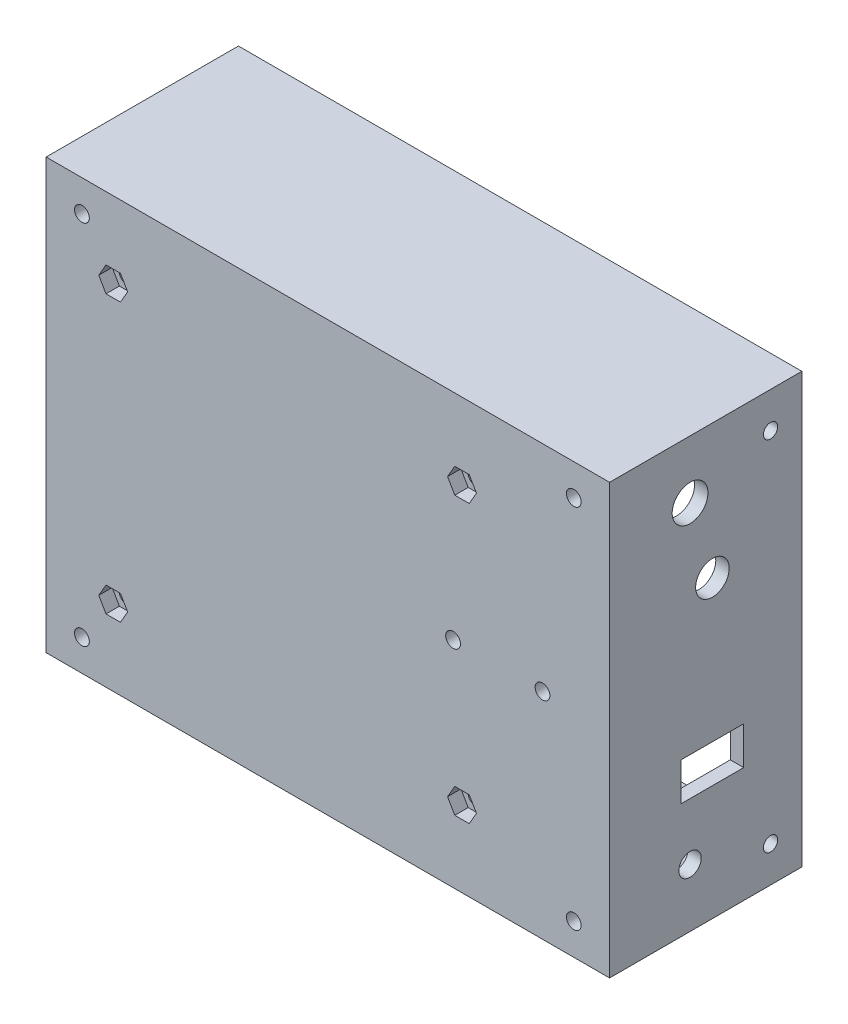
SolidWorks part; units mm, degrees
ref_plane "Front Plane" through (0, 0, 0) normal (0, 0, 1) x (1, 0, 0)
ref_plane "Top Plane" through (0, 0, 0) normal (0, 1, 0) x (1, 0, 0)
ref_plane "Right Plane" through (0, 0, 0) normal (1, 0, 0) x (0, 0, -1)
sketch "Sketch1" plane through (0, 0, 0) normal (0, 0, 1) x (1, 0, 0)
  line L1 (-60, -45) -> (60, -45)
  line L2 (-60, -45) -> (-60, 45)
  line L3 (-60, 45) -> (60, 45)
  line L4 (60, -45) -> (60, 45)
  line L5 (-60, -45) -> (60, 45) construction
  line L6 (-60, 45) -> (60, -45) construction
  line L7 (-48, -31) -> (30, -31)
  line L8 (-48, -31) -> (-48, 31)
  line L9 (-48, 31) -> (30, 31)
  line L10 (30, -31) -> (30, 31)
  line L11 (-48, -31) -> (30, 31) construction
  line L12 (-48, 31) -> (30, -31) construction
  circle A0 centre (-48, 31) radius 1.65
  circle A1 centre (30, 31) radius 1.65
  circle A2 centre (30, -31) radius 1.65
  circle A3 centre (-48, -31) radius 1.65
  circle A4 centre (-55, 41) radius 1.65
  circle A5 centre (55, 41) radius 1.65
  circle A6 centre (55, -41) radius 1.65
  circle A7 centre (-55, -41) radius 1.65
  point P0 (0, 0)
  point P6 (-9, 0)
  dimension "D7" = 3.3
  dimension "D8" = 4
  dimension "D9" = 5
  dimension "D10" = 5
  dimension "D11" = 4
  dimension "D12" = 3.3
  dimension "D13" = 5
  dimension "D14" = 4
  dimension "D15" = 4
  dimension "D16" = 5
  dimension "D1" = 90
  dimension "D2" = 120
  dimension "D3" = 62
  dimension "D4" = 78
  dimension "D5" = 14
  dimension "D6" = 30
extrude "Boss-Extrude2" add sketch "Sketch1" along normal blind 4 contours L1 L4 L3 L2 A3 L8 A0 L9 A1 L10 A2 L7 | A3 L7 A2 L10 A1 L9 A0 L8 region at (-58.5, 0, 0) region at (-9, 0, 0)
sketch "Sketch2" plane through (0, 0, 4) normal (0, 0, 1) x (1, 0, 0)
  line L1 (60, -45) -> (-60, -45)
  line L2 (60, -45) -> (60, 45)
  line L3 (60, 45) -> (-60, 45)
  line L4 (-60, -45) -> (-60, 45)
  line L5 (60, -45) -> (-60, 45) construction
  line L6 (60, 45) -> (-60, -45) construction
  line L7 (63, -48) -> (-63, -48)
  line L8 (63, -48) -> (63, 48)
  line L9 (63, 48) -> (-63, 48)
  line L10 (-63, -48) -> (-63, 48)
  line L11 (63, -48) -> (-63, 48) construction
  line L12 (63, 48) -> (-63, -48) construction
  point P0 (0, 0)
  point P7 (0, 0)
  dimension "D1" = 3
  dimension "D2" = 3
extrude "Boss-Extrude3" add sketch "Sketch2" against normal blind 43
sketch "Sketch3" plane through (-63, 0, 0) normal (-1, 0, 0) x (0, 0, 1)
  line L0 (-39, 48) -> (-39, -48) construction
  line L1 (-39, 48) -> (4, 48) construction
  line L2 (-39, -48) -> (4, -48) construction
  circle A0 centre (-32, -40) radius 1.6
  circle A1 centre (-32, 40) radius 1.6
  dimension "D1" = 3.2
  dimension "D2" = 7
  dimension "D3" = 8
  dimension "D4" = 8
  dimension "D5" = 7
  dimension "D6" = 3.2
extrude "Cut-Extrude1" cut sketch "Sketch3" against normal up to surface (126 mm away) up to face at (63, 0, -17.5)
sketch "Sketch4" plane through (63, 0, 0) normal (1, 0, 0) x (0, 0, -1)
  line L0 (39, -48) -> (39, 48) construction
  line L6 (39, 48) -> (-4, 48) construction
  line L9 (12, -22.25) -> (26, -22.25)
  line L10 (12, -22.25) -> (12, -13.75)
  line L11 (12, -13.75) -> (26, -13.75)
  line L12 (26, -22.25) -> (26, -13.75)
  line L13 (12, -22.25) -> (26, -13.75) construction
  line L14 (12, -13.75) -> (26, -22.25) construction
  line L19 (39, -48) -> (-4, -48) construction
  circle A1 centre (19, 18) radius 3.75
  point P0 (21, 0)
  point P8 (19, -18)
  dimension "D4" = 7.5
  dimension "D5" = 8.5
  dimension "D6" = 20
  dimension "D7" = 14
  dimension "D8" = 30
  dimension "D3" = 30
  dimension "D10" = 20
extrude "Cut-Extrude3" cut sketch "Sketch4" against normal blind 10
sketch "Sketch5" plane through (63, 0, 0) normal (1, 0, 0) x (0, 0, -1)
  line L0 (39, -48) -> (39, 48) construction
  line L1 (39, 48) -> (-4, 48) construction
  circle A0 centre (14, 35) radius 4
  dimension "D1" = 8
  dimension "D2" = 25
  dimension "D3" = 13
extrude "Cut-Extrude4" cut sketch "Sketch5" against normal blind 10
sketch "Sketch6" plane through (63, 0, 0) normal (1, 0, 0) x (0, 0, -1)
  line L0 (22, -35) -> (6, -35)
  line L1 (39, -48) -> (39, 48) construction
  line L3 (39, -48) -> (-4, -48) construction
  line L4 (-4, -48) -> (-4, 48) construction
  circle A0 centre (14, -35) radius 2.5
  point P3 (14, -35)
  dimension "D5" = 5
  dimension "D2" = 25
  dimension "D1" = 16
  dimension "D3" = 13
extrude "Cut-Extrude5" cut sketch "Sketch6" against normal blind 10 contours L0 A0 | A0 region at (63, -36.061, -14)
sketch "Sketch8" plane through (0, 0, 0) normal (0, 0, -1) x (-1, 0, 0)
  line L1 (-60, -45) -> (-60, 45) construction
  circle A0 centre (-48, 0) radius 1.65
  circle A1 centre (-28, 0) radius 1.65
  circle A2 centre (-30, 31) radius 1.65 construction
  dimension "D1" = 3.3
  dimension "D2" = 3.3
  dimension "D3" = 20
  dimension "D4" = 31
  dimension "D5" = 31
  dimension "D6" = 12
extrude "Cut-Extrude6" cut sketch "Sketch8" against normal blind 10
sketch "Sketch9" plane through (0, 0, 0) normal (0, 0, -1) x (-1, 0, 0)
  line L0 (60, -45) -> (-60, -45) construction
  line L1 (-46.3834, 2.8) -> (-49.6166, 2.8)
  line L2 (-49.6166, 2.8) -> (-51.2332, 0)
  line L3 (-51.2332, 0) -> (-49.6166, -2.8)
  line L4 (-49.6166, -2.8) -> (-46.3834, -2.8)
  line L5 (-46.3834, -2.8) -> (-44.7668, 0)
  line L6 (-44.7668, 0) -> (-46.3834, 2.8)
  line L7 (-26.3834, 2.8) -> (-29.6166, 2.8)
  line L8 (-29.6166, 2.8) -> (-31.2332, 0)
  line L9 (-31.2332, 0) -> (-29.6166, -2.8)
  line L10 (-29.6166, -2.8) -> (-26.3834, -2.8)
  line L11 (-26.3834, -2.8) -> (-24.7668, 0)
  line L12 (-24.7668, 0) -> (-26.3834, 2.8)
  line L13 (-45.2287, 4.8) -> (-50.7713, 4.8)
  line L14 (-50.7713, 4.8) -> (-53.5426, 0)
  line L15 (-53.5426, 0) -> (-50.7713, -4.8)
  line L16 (-50.7713, -4.8) -> (-45.2287, -4.8)
  line L17 (-45.2287, -4.8) -> (-42.4574, 0)
  line L18 (-42.4574, 0) -> (-45.2287, 4.8)
  line L19 (-25.2287, 4.8) -> (-30.7713, 4.8)
  line L20 (-30.7713, 4.8) -> (-33.5426, 0)
  line L21 (-33.5426, 0) -> (-30.7713, -4.8)
  line L22 (-30.7713, -4.8) -> (-25.2287, -4.8)
  line L23 (-25.2287, -4.8) -> (-22.4574, 0)
  line L24 (-22.4574, 0) -> (-25.2287, 4.8)
  line L25 (60, -45) -> (-60, -45) construction
  line L26 (-51.7668, 41) -> (-53.3834, 43.8)
  line L27 (-53.3834, 43.8) -> (-56.6166, 43.8)
  line L28 (-56.6166, 43.8) -> (-58.2332, 41)
  line L29 (-58.2332, 41) -> (-56.6166, 38.2)
  line L30 (-56.6166, 38.2) -> (-53.3834, 38.2)
  line L31 (-53.3834, 38.2) -> (-51.7668, 41)
  line L32 (-50.6121, 41) -> (-52.8061, 44.8)
  line L33 (-52.8061, 44.8) -> (-57.1939, 44.8)
  line L34 (-57.1939, 44.8) -> (-59.3879, 41)
  line L35 (-59.3879, 41) -> (-57.1939, 37.2)
  line L36 (-57.1939, 37.2) -> (-52.8061, 37.2)
  line L37 (-52.8061, 37.2) -> (-50.6121, 41)
  line L38 (58.2332, 41) -> (56.6166, 43.8)
  line L39 (56.6166, 43.8) -> (53.3834, 43.8)
  line L40 (53.3834, 43.8) -> (51.7668, 41)
  line L41 (51.7668, 41) -> (53.3834, 38.2)
  line L42 (53.3834, 38.2) -> (56.6166, 38.2)
  line L43 (56.6166, 38.2) -> (58.2332, 41)
  line L44 (52.8061, 44.8) -> (50.6121, 41)
  line L45 (50.6121, 41) -> (52.8061, 37.2)
  line L46 (52.8061, 37.2) -> (57.1939, 37.2)
  line L47 (57.1939, 37.2) -> (59.3879, 41)
  line L48 (59.3879, 41) -> (57.1939, 44.8)
  line L49 (57.1939, 44.8) -> (52.8061, 44.8)
  line L50 (53.3834, -38.2) -> (51.7668, -41)
  line L51 (51.7668, -41) -> (53.3834, -43.8)
  line L52 (53.3834, -43.8) -> (56.6166, -43.8)
  line L53 (56.6166, -43.8) -> (58.2332, -41)
  line L54 (58.2332, -41) -> (56.6166, -38.2)
  line L55 (56.6166, -38.2) -> (53.3834, -38.2)
  line L56 (50.6121, -41) -> (52.8061, -44.8)
  line L57 (52.8061, -44.8) -> (57.1939, -44.8)
  line L58 (57.1939, -44.8) -> (59.3879, -41)
  line L59 (59.3879, -41) -> (57.1939, -37.2)
  line L60 (57.1939, -37.2) -> (52.8061, -37.2)
  line L61 (52.8061, -37.2) -> (50.6121, -41)
  line L62 (-53.3834, -38.2) -> (-56.6166, -38.2)
  line L63 (-56.6166, -38.2) -> (-58.2332, -41)
  line L64 (-58.2332, -41) -> (-56.6166, -43.8)
  line L65 (-56.6166, -43.8) -> (-53.3834, -43.8)
  line L66 (-53.3834, -43.8) -> (-51.7668, -41)
  line L67 (-51.7668, -41) -> (-53.3834, -38.2)
  line L68 (-52.8061, -37.2) -> (-57.1939, -37.2)
  line L69 (-57.1939, -37.2) -> (-59.3879, -41)
  line L70 (-59.3879, -41) -> (-57.1939, -44.8)
  line L71 (-57.1939, -44.8) -> (-52.8061, -44.8)
  line L72 (-52.8061, -44.8) -> (-50.6121, -41)
  line L73 (-50.6121, -41) -> (-52.8061, -37.2)
  circle A0 centre (-48, 0) radius 2.8 construction
  circle A1 centre (-28, 0) radius 2.8 construction
  circle A2 centre (-48, 0) radius 4.8 construction
  circle A3 centre (-28, 0) radius 4.8 construction
  circle A4 centre (-55, 41) radius 2.8 construction
  circle A5 centre (-55, 41) radius 3.8 construction
  circle A6 centre (55, 41) radius 2.8 construction
  circle A7 centre (55, 41) radius 3.8 construction
  circle A8 centre (55, -41) radius 2.8 construction
  circle A9 centre (55, -41) radius 3.8 construction
  circle A10 centre (-55, -41) radius 2.8 construction
  circle A11 centre (-55, -41) radius 3.8 construction
  dimension "D1" = 5.6
  dimension "D2" = 2
  dimension "D3" = 5.6
  dimension "D4" = 1
extrude "Boss-Extrude4" add sketch "Sketch9" along normal blind 3
sketch "Sketch10" plane through (0, 0, 4) normal (0, 0, 1) x (1, 0, 0)
  line L0 (63, 48) -> (-63, 48) construction
  line L1 (-44.7668, 31) -> (-46.3834, 33.8)
  line L2 (-46.3834, 33.8) -> (-49.6166, 33.8)
  line L3 (-49.6166, 33.8) -> (-51.2332, 31)
  line L4 (-51.2332, 31) -> (-49.6166, 28.2)
  line L5 (-49.6166, 28.2) -> (-46.3834, 28.2)
  line L6 (-46.3834, 28.2) -> (-44.7668, 31)
  line L7 (33.2332, 31) -> (31.6166, 33.8)
  line L8 (31.6166, 33.8) -> (28.3834, 33.8)
  line L9 (28.3834, 33.8) -> (26.7668, 31)
  line L10 (26.7668, 31) -> (28.3834, 28.2)
  line L11 (28.3834, 28.2) -> (31.6166, 28.2)
  line L12 (31.6166, 28.2) -> (33.2332, 31)
  line L25 (-44.7668, -31) -> (-46.3834, -28.2)
  line L26 (-46.3834, -28.2) -> (-49.6166, -28.2)
  line L27 (-49.6166, -28.2) -> (-51.2332, -31)
  line L28 (-51.2332, -31) -> (-49.6166, -33.8)
  line L29 (-49.6166, -33.8) -> (-46.3834, -33.8)
  line L30 (-46.3834, -33.8) -> (-44.7668, -31)
  line L31 (33.2332, -31) -> (31.6166, -28.2)
  line L32 (31.6166, -28.2) -> (28.3834, -28.2)
  line L33 (28.3834, -28.2) -> (26.7668, -31)
  line L34 (26.7668, -31) -> (28.3834, -33.8)
  line L35 (28.3834, -33.8) -> (31.6166, -33.8)
  line L36 (31.6166, -33.8) -> (33.2332, -31)
  circle A0 centre (-48, 31) radius 2.8 construction
  circle A1 centre (30, 31) radius 2.8 construction
  circle A4 centre (-48, -31) radius 2.8 construction
  circle A5 centre (30, -31) radius 2.8 construction
  dimension "D2" = 5.6
extrude "Cut-Extrude8" cut sketch "Sketch10" against normal blind 3
sketch "Sketch12" plane through (0, 0, 0) normal (0, 0, -1) x (-1, 0, 0)
  circle A0 centre (-30, 31) radius 1.65
  circle A1 centre (48, 31) radius 1.65
  circle A2 centre (48, -31) radius 1.65
  circle A3 centre (-30, -31) radius 1.65
  circle A4 centre (-30, -31) radius 4
  circle A5 centre (48, -31) radius 4
  circle A6 centre (48, 31) radius 4
  circle A7 centre (-30, 31) radius 4
  dimension "D1" = 8
extrude "Boss-Extrude11" add sketch "Sketch12" along normal blind 3.5
sketch "Sketch13" plane through (60, 0, 0) normal (-1, 0, 0) x (0, 0, 1)
  line L1 (-19, 29) -> (-9, 29)
  line L2 (-19, 29) -> (-19, 41)
  line L3 (-19, 41) -> (-9, 41)
  line L4 (-9, 29) -> (-9, 41)
  line L5 (-19, 29) -> (-9, 41) construction
  line L6 (-19, 41) -> (-9, 29) construction
  line L7 (-22, 27) -> (-6, 27)
  line L8 (-22, 27) -> (-22, 43)
  line L9 (-22, 43) -> (-6, 43)
  line L10 (-6, 27) -> (-6, 43)
  line L11 (-22, 27) -> (-6, 43) construction
  line L12 (-22, 43) -> (-6, 27) construction
  point P0 (-14, 35)
  point P6 (-14, 35)
  dimension "D1" = 12
  dimension "D2" = 10
  dimension "D3" = 2
  dimension "D4" = 3
extrude "Boss-Extrude12" add sketch "Sketch13" along normal blind 1
chamfer "Chamfer1" distance 1 angle 45 2 edges at (59, 35, -6) (59, 35, -22)
sketch "Sketch16" plane through (0, 0, 0) normal (0, 0, -1) x (-1, 0, 0)
  line L0 (-50.6121, 42) -> (44, 42)
  line L1 (44, 42) -> (44, 30.25)
  line L2 (47.25, 27) -> (57, 27)
  line L3 (57, 27) -> (57, -27)
  line L4 (57, -27) -> (47.25, -27)
  line L5 (44, -30.25) -> (44, -42)
  line L6 (44, -42) -> (-50.6121, -42)
  line L7 (-50.6121, -42) -> (-50.6121, -37.2)
  line L8 (-50.6121, -37.2) -> (-57, -37.2)
  line L9 (-57, -37.2) -> (-57, 37.2)
  line L10 (-57, 37.2) -> (-50.6121, 37.2)
  line L11 (-50.6121, 37.2) -> (-50.6121, 42)
  line L12 (-57, 4.8) -> (-22.4574, 4.8)
  line L13 (-22.4574, 4.8) -> (-22.4574, -4.8)
  line L14 (-22.4574, -4.8) -> (-57, -4.8)
  line L15 (-22.4574, 1.5) -> (57, 1.5)
  line L16 (57, 1.5) -> (57, -1.5)
  line L17 (57, -1.5) -> (-22.4574, -1.5)
  line L18 (-60, 45) -> (-60, -45)
  line L19 (60, -45) -> (-60, -45) construction
  line L20 (-60, -45) -> (-60, 45) construction
  line L21 (-60, -45) -> (60, -45)
  line L22 (60, -45) -> (60, 45)
  line L23 (60, 45) -> (-60, 45)
  line L24 (-1.5, 42) -> (-1.5, -42)
  line L25 (-1.5, -42) -> (1.5, -42)
  line L26 (1.5, -42) -> (1.5, 42)
  line L27 (1.5, 42) -> (-1.5, 42)
  line L28 (-45.2287, 4.8) -> (-50.7713, 4.8) construction
  line L29 (-50.7713, -4.8) -> (-45.2287, -4.8) construction
  line L30 (-60, -45) -> (-60, 45) construction
  line L31 (-52.8061, -37.2) -> (-57.1939, -37.2) construction
  line L32 (-57.1939, 37.2) -> (-52.8061, 37.2) construction
  line L33 (-50.6121, 41) -> (-52.8061, 37.2)
  line L34 (-52.8061, -37.2) -> (-50.6121, -41)
  line L35 (-22.4574, -1.5) -> (-24.3627, -4.8)
  line L36 (-24.3627, 4.8) -> (-22.4574, 1.5)
  line L37 (-22.4574, 0) -> (-25.2287, 4.8) construction
  line L38 (-25.2287, -4.8) -> (-22.4574, 0) construction
  circle A0 centre (48, -31) radius 4 construction
  circle A1 centre (48, 31) radius 4 construction
  arc A2 (47.25, -27) -> (44, -30.25) centre (47.25, -30.25) ccw
  arc A3 (44, 30.25) -> (47.25, 27) centre (47.25, 30.25) ccw
  circle M27 centre (-30, -31) radius 4
  line M34 (-45.2287, -4.8) -> (-50.7713, -4.8)
  line M37 (-50.7713, 4.8) -> (-45.2287, 4.8)
  line M40 (-25.2287, -4.8) -> (-30.7713, -4.8)
  line M43 (-30.7713, 4.8) -> (-25.2287, 4.8)
  line M44 (-50.6121, 41) -> (-52.8061, 37.2)
  line M45 (-52.8061, 37.2) -> (-57.1939, 37.2)
  line M54 (52.8061, 37.2) -> (50.6121, 41)
  line M55 (50.6121, 41) -> (52.8061, 44.8)
  line M56 (50.6121, -41) -> (52.8061, -37.2)
  line M61 (52.8061, -44.8) -> (50.6121, -41)
  line M62 (-52.8061, -37.2) -> (-50.6121, -41)
  line M67 (-57.1939, -37.2) -> (-52.8061, -37.2)
  circle M69 centre (-30, 31) radius 4
  dimension "D9" = 3.25
  dimension "D1" = 3
  dimension "D2" = 3
  dimension "D3" = 3
  dimension "D4" = 1.5
  dimension "D5" = 1.5
  dimension "D6" = 3
  dimension "D7" = 3
  dimension "D8" = 3
extrude "Cut-Extrude11" cut sketch "Sketch16" against normal blind 3 contours L24 L0 L11 L10 L9 L12 L13 L15 M45 M37 M43 M69 | L26 L15 L3 L2 L1 L0 M54 M55 | L26 L6 L5 L4 L3 L17 M61 M56 | L24 L17 L13 L14 L9 L8 L7 L6 M40 M34 M67 M27 | L7 L8 M62 | L10 L11 M44 | L12 L36 L13 | L13 L35 L14 region at (28.283, 22.2897, 0) region at (51.3434, 38.4667, 0) region at (-27.2507, 20.5467, 0) region at (23.0925, 3.7, 0) region at (28.283, -22.2897, 0) region at (-27.2507, -20.5467, 0) region at (23.0925, -3.7, 0) region at (51.3434, -38.4667, 0)
sketch "Sketch17" plane through (0, 45, 0) normal (0, -1, 0) x (1, 0, 0)
  line L1 (-57, -36) -> (57, -36)
  line L2 (-57, -36) -> (-57, -3)
  line L3 (-57, -3) -> (57, -3)
  line L4 (57, -36) -> (57, -3)
  line L5 (-60, 0) -> (60, 0) construction
  line L6 (60, -39) -> (60, 0) construction
  line L7 (-60, -39) -> (-60, 0) construction
  line L8 (60, -39) -> (-60, -39) construction
  line L9 (-1.5, 3) -> (-1.5, 0) construction
  line L10 (-57, -18) -> (57, -18)
  line L11 (-57, -18) -> (-57, -21)
  line L12 (-57, -21) -> (57, -21)
  line L13 (57, -18) -> (57, -21)
  line L14 (-1.5, -3) -> (1.5, -3)
  line L15 (-1.5, -3) -> (-1.5, -36)
  line L16 (-1.5, -36) -> (1.5, -36)
  line L17 (1.5, -3) -> (1.5, -36)
  dimension "D1" = 3
  dimension "D2" = 3
  dimension "D3" = 3
  dimension "D4" = 3
  dimension "D5" = 3
  dimension "D6" = 3
  dimension "D7" = 15
extrude "Cut-Extrude13" cut sketch "Sketch17" against normal blind 2 contours L15 L12 L2 L1 | L15 L3 L2 L10 | L3 L17 L10 L4 | L12 L17 L1 L4 region at (-29.25, 45, -28.5) region at (29.25, 45, -28.5) region at (-29.25, 45, -10.5) region at (29.25, 45, -10.5)
sketch "Sketch20" plane through (0, -45, 0) normal (0, 1, 0) x (1, 0, 0)
  line L0 (-57, -3) -> (-57, 0) construction
  line L1 (-57, 36) -> (57, 36)
  line L2 (-57, 36) -> (-57, 3)
  line L3 (-57, 3) -> (57, 3)
  line L4 (57, 36) -> (57, 3)
  line L5 (-1.5, 36) -> (1.5, 36)
  line L6 (-1.5, 36) -> (-1.5, 3)
  line L7 (-1.5, 3) -> (1.5, 3)
  line L8 (1.5, 36) -> (1.5, 3)
  line L9 (-57, 21) -> (57, 21)
  line L10 (-57, 21) -> (-57, 18)
  line L11 (-57, 18) -> (57, 18)
  line L12 (57, 21) -> (57, 18)
  line L13 (57, -3) -> (57, 0) construction
  line L14 (1.5, 36) -> (57, 36) construction
  line L16 (-57, 21) -> (-1.5, 21) construction
  line L17 (-57, 3) -> (-1.5, 3) construction
  line L18 (1.5, 21) -> (57, 21) construction
  line L19 (-57, 18) -> (-1.5, 18) construction
  line L20 (-1.5, 3) -> (-1.5, 18) construction
  line L21 (1.5, 3) -> (1.5, 18) construction
extrude "Cut-Extrude14" cut sketch "Sketch20" against normal blind 2 contours L2 L9 L6 L1 | L8 L9 L4 L1 | L11 L8 L3 L4 | L11 L2 L3 L6 region at (-29.25, -45, -28.5) region at (29.25, -45, -28.5) region at (-29.25, -45, -10.5) region at (29.25, -45, -10.5)
sketch "Sketch21" plane through (-60, 0, 0) normal (1, 0, 0) x (0, 0, -1)
  line L0 (0, -45) -> (0, 45) construction
  line L1 (28, 42) -> (3, 42)
  line L2 (28, 42) -> (28, -42)
  line L3 (28, -42) -> (3, -42)
  line L4 (3, 42) -> (3, -42)
  line L5 (28, 36) -> (36, 36)
  line L6 (28, 36) -> (28, -36)
  line L7 (28, -36) -> (36, -36)
  line L8 (36, 36) -> (36, -36)
  line L9 (3, 1.5) -> (36, 1.5)
  line L10 (3, 1.5) -> (3, -1.5)
  line L11 (3, -1.5) -> (36, -1.5)
  line L12 (36, 1.5) -> (36, -1.5)
  line L13 (21, 42) -> (18, 42)
  line L14 (21, 42) -> (21, -42)
  line L15 (21, -42) -> (18, -42)
  line L16 (18, 42) -> (18, -42)
  line L17 (39, 45) -> (0, 45) construction
  line L18 (39, 45) -> (39, -45) construction
  line L19 (39, -45) -> (0, -45) construction
  line L20 (-3, -1.5) -> (0, -1.5) construction
  dimension "D1" = 3
  dimension "D2" = 3
  dimension "D3" = 3
  dimension "D4" = 3
  dimension "D5" = 6
  dimension "D6" = 6
  dimension "D7" = 8
  dimension "D8" = 3
  dimension "D9" = 3
  dimension "D10" = 15
extrude "Cut-Extrude15" cut sketch "Sketch21" against normal blind 2 contours L2 L9 L8 L5 | L1 L14 L9 L2 | L11 L2 L7 L8 | L11 L14 L3 L2 | L16 L11 L4 L3 | L16 L1 L4 L9 region at (-60, 21.75, -24.5) region at (-60, 18.75, -32) region at (-60, 21.75, -10.5) region at (-60, -21.75, -24.5) region at (-60, -18.75, -32) region at (-60, -21.75, -10.5)
chamfer "Chamfer6" distance 1.5 angle 45 14 edges at (29.25, -47, -18) (29.25, -47, -36) (-29.25, -47, -36) (-29.25, -47, -18) (-62, 21.75, -18) (-62, -21.75, -18) (-62, -39, -28) (-62, -18.75, -36) (-62, 39, -28) (-62, 18.75, -36) (-29.25, 47, -18) (29.25, 47, -18) (-29.25, 47, -36) (29.25, 47, -36)
